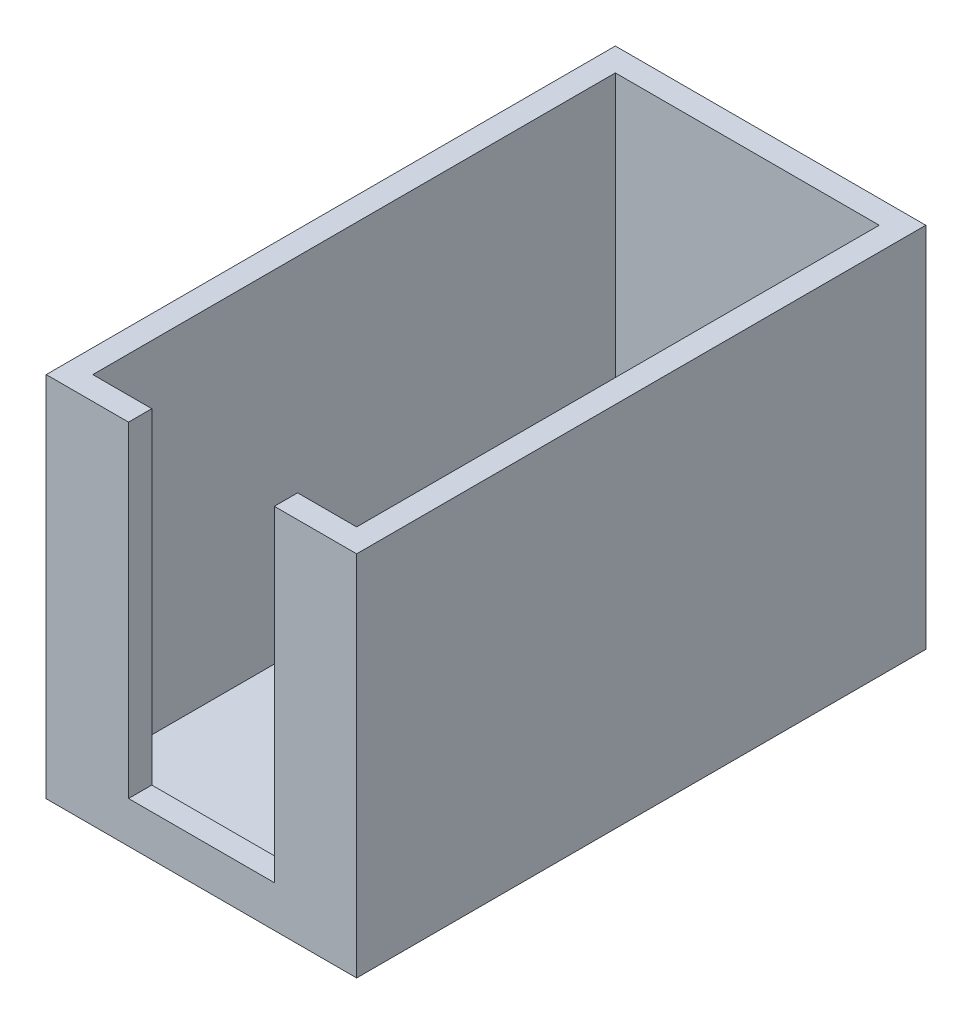
SolidWorks part; units mm, degrees
ref_plane "Front Plane" through (0, 0, 0) normal (0, 0, 1) x (1, 0, 0)
ref_plane "Top Plane" through (0, 0, 0) normal (0, 1, 0) x (1, 0, 0)
ref_plane "Right Plane" through (0, 0, 0) normal (1, 0, 0) x (0, 0, -1)
sketch "Sketch1" plane through (0, 0, 0) normal (0, 1, 0) x (1, 0, 0)
  line L1 (-10.2, 20.2) -> (10.2, 20.2)
  line L2 (-10.2, 20.2) -> (-10.2, -20.2)
  line L3 (-10.2, -20.2) -> (10.2, -20.2)
  line L4 (10.2, 20.2) -> (10.2, -20.2)
  line L5 (-10.2, 20.2) -> (10.2, -20.2) construction
  line L6 (-10.2, -20.2) -> (10.2, 20.2) construction
  point P0 (0, 0)
  dimension "D1" = 20.4
  dimension "D2" = 40.4
extrude "Extrude-Thin1" add sketch "Sketch1" along normal blind 28.4 thin thin type one direction wall 1.8
extrude "Boss-Extrude1" add sketch "Sketch1<2>" along normal blind 2
sketch "Sketch1<2>" plane through (0, 0, 0) normal (0, 1, 0) x (1, 0, 0) same geometry as "Sketch1"
sketch "Sketch3" plane through (0, 28.4, 0) normal (0, 1, 0) x (1, 0, 0)
  line L1 (-5.6363, -34.2811) -> (5.6363, -34.2811)
  line L2 (-5.6363, -34.2811) -> (-5.6363, -14.9368)
  line L3 (-5.6363, -14.9368) -> (5.6363, -14.9368)
  line L4 (5.6363, -34.2811) -> (5.6363, -14.9368)
  line L5 (-5.6363, -34.2811) -> (5.6363, -14.9368) construction
  line L6 (-5.6363, -14.9368) -> (5.6363, -34.2811) construction
  point P0 (0, -24.609)
extrude "Cut-Extrude1" cut sketch "Sketch3" against normal offset from surface (25.2 mm away) 1.2 up to face at (0, 2, 0)
